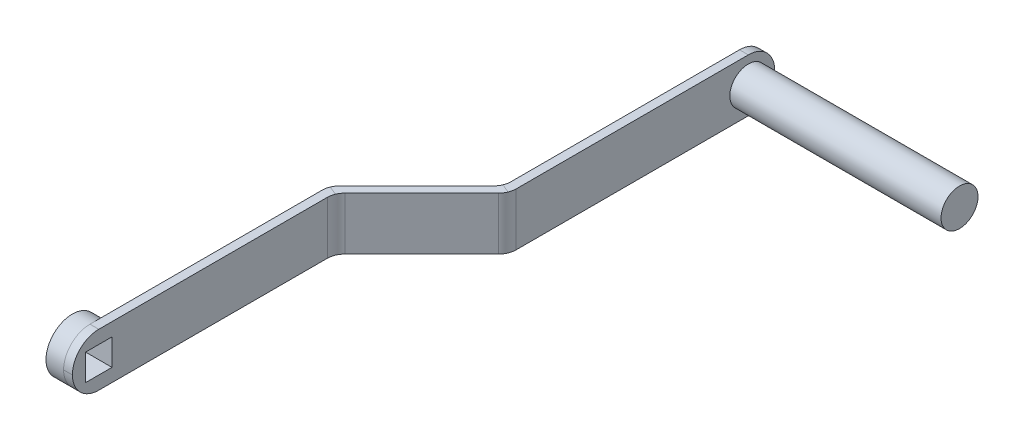
SolidWorks part; units mm, degrees
ref_plane "Front Plane" through (0, 0, 0) normal (0, 0, 1) x (1, 0, 0)
ref_plane "Top Plane" through (0, 0, 0) normal (0, 1, 0) x (1, 0, 0)
ref_plane "Right Plane" through (0, 0, 0) normal (1, 0, 0) x (0, 0, -1)
sketch "Sketch2" plane through (0, 0, 0) normal (0, 1, 0) x (1, 0, 0)
  line L0 (0, -75) -> (0, 75)
  line L1 (0, 75) -> (49.4975, 124.4975)
  line L2 (49.4975, 124.4975) -> (49.4975, 274.4975)
  point P4 (0, 0)
  dimension "D1" = 150
  dimension "D2" = 150
  dimension "D3" = 135
  dimension "D4" = 70
ref_plane "Plane1" through (0, 0, 75) normal (0, 0, 1) x (1, 0, 0)
sketch "Sketch6" plane through (0, 0, 75) normal (0, 0, 1) x (1, 0, 0)
  line L1 (-2.5, 15) -> (2.5, 15)
  line L2 (-2.5, 15) -> (-2.5, -15)
  line L3 (-2.5, -15) -> (2.5, -15)
  line L4 (2.5, 15) -> (2.5, -15)
  line L5 (-2.5, 15) -> (2.5, -15) construction
  line L6 (-2.5, -15) -> (2.5, 15) construction
  point P0 (0, 0)
  dimension "D1" = 30
  dimension "D2" = 5
sweep "Sweep1" add profiles "Sketch6" path "Sketch2"
sketch "Sketch7" plane through (-2.5, 0, 0) normal (-1, 0, 0) x (0, 0, 1)
  line L0 (75, 15) -> (-76.0355, 15) construction
  line L1 (75, 15) -> (75, -15) construction
  line L3 (52.5, 7.5) -> (67.5, 7.5)
  line L4 (52.5, 7.5) -> (52.5, -7.5)
  line L5 (52.5, -7.5) -> (67.5, -7.5)
  line L6 (67.5, 7.5) -> (67.5, -7.5)
  line L7 (52.5, 7.5) -> (67.5, -7.5) construction
  line L8 (52.5, -7.5) -> (67.5, 7.5) construction
  circle A0 centre (60, 0) radius 15
  dimension "D1" = 30
  dimension "D2" = 15
  dimension "D3" = 15
extrude "Boss-Extrude1" add sketch "Sketch7" along normal blind 10 contours A0
extrude "Cut-Extrude1" cut sketch "Sketch7<3>" against normal through all both and the other way through all contours L3 L6 L5 L4
sketch "Sketch7<3>" plane through (-2.5, 0, 0) normal (-1, 0, 0) x (0, 0, 1) same geometry as "Sketch7"
fillet "Fillet1" radius 10 4 edges at (51.9975, 0, -123.4619) (2.5, 0, -73.9645) (-2.5, 0, -76.0355) (46.9975, 0, -125.533)
fillet "Fillet2" radius 15 4 edges at (0, 15, 75) (0, -15, 75) (49.4975, -15, -274.4975) (49.4975, 15, -274.4975)
sketch "Sketch9" plane through (51.9975, 0, 0) normal (1, 0, 0) x (0, 0, -1)
  line L0 (259.4975, 15) -> (259.4975, -15) construction
  circle A0 centre (259.4975, 0) radius 10.5
  dimension "D1" = 21
extrude "Boss-Extrude2" add sketch "Sketch9" along normal blind 120
